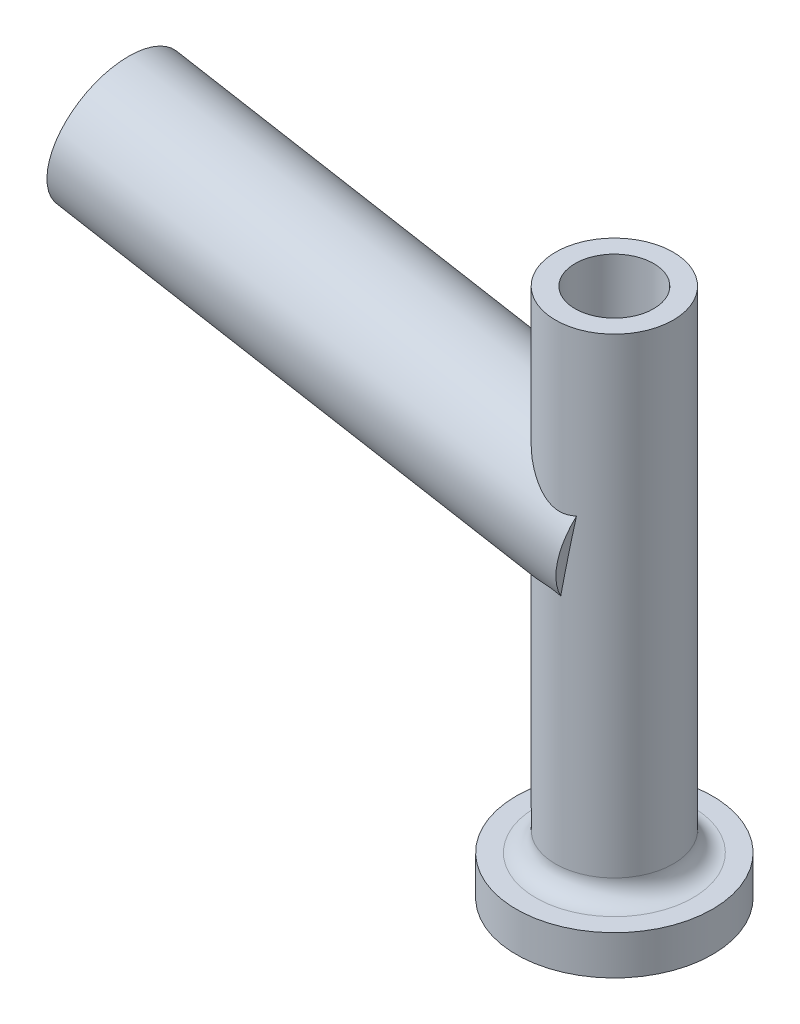
SolidWorks part; units mm, degrees
ref_plane "Front Plane" through (0, 0, 0) normal (0, 0, 1) x (1, 0, 0)
ref_plane "Top Plane" through (0, 0, 0) normal (0, 1, 0) x (1, 0, 0)
ref_plane "Right Plane" through (0, 0, 0) normal (1, 0, 0) x (0, 0, -1)
sketch "Sketch14" plane through (0, 0, 0) normal (0, 0, 1) x (1, 0, 0)
  line L0 (0, -135) -> (0, 135) construction
  line L6 (30, -115) -> (30, 135)
  line L7 (30, 135) -> (20, 135)
  line L8 (20, 135) -> (20, -135)
  line L9 (20, -135) -> (50, -135)
  line L10 (50, -135) -> (50, -115)
  line L11 (50, -115) -> (30, -115)
  dimension "D1" = 10
  dimension "D2" = 270
  dimension "D3" = 30
  dimension "D4" = 20
  dimension "D5" = 20
revolve "Revolve3" add sketch "Sketch14" angle 360 about L0
ref_axis "Axis2" through (0, 0, -55) along (0, 0, 1)
ref_plane "Plane7" through (0, 0, 0) normal (0.9848, -0.1736, 0) x (0, 0, -1)
sketch "Sketch11" plane through (0.0697, 0.3953, -0.0708) normal (0.9848, -0.1736, 0) x (-0.0302, -0.171, -0.9848)
  line L0 (-23.0864, 130.5217) -> (0, -0.4076) construction
  circle A0 centre (-5.7215, 32.0409) radius 35
  ellipse E2 centre (-23.0864, 130.5217) end of major axis (-3.3902, 133.9946) minor radius 3.473 construction
  dimension "D1" = 70
  dimension "D2" = 100
extrude "Boss-Extrude2" add sketch "Sketch11" against normal blind 263.3658
fillet "Fillet2" radius 10 1 edges at (30, -115, 0) tangent propagation no
sketch "Sketch15" plane through (0, 135, 0) normal (0, 1, 0) x (1, 0, 0)
  circle A0 centre (0, 0) radius 20 construction
  circle A1 centre (0, 0) radius 20
extrude "Cut-Extrude1" cut sketch "Sketch15" against normal through all
